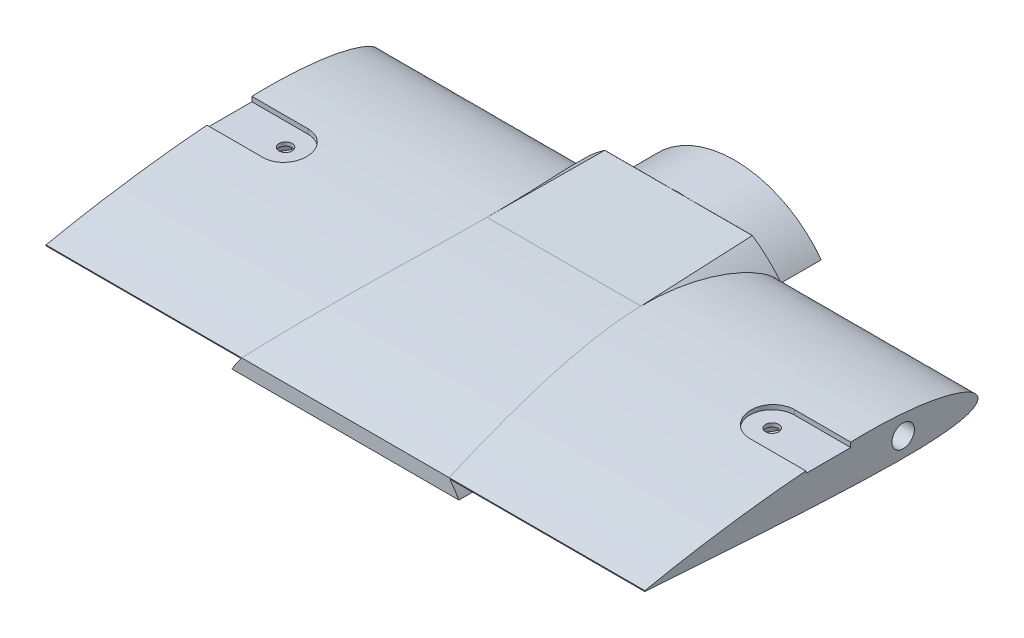
SolidWorks part; units mm, degrees
ref_plane "Front Plane" through (0, 0, 0) normal (0, 0, 1) x (1, 0, 0)
ref_plane "Top Plane" through (0, 0, 0) normal (0, 1, 0) x (1, 0, 0)
ref_plane "Right Plane" through (0, 0, 0) normal (1, 0, 0) x (0, 0, -1)
sketch "Sketch4" plane through (0, 0, 0) normal (0, 0, 1) x (1, 0, 0)
  line L0 (-30.3109, 17.5) -> (30.3109, 17.5)
  arc A1 (30.3109, 17.5) -> (-30.3109, 17.5) centre (0, 0) ccw
  dimension "D1" = 35
  dimension "D2" = 17.5
extrude "Exterior" add sketch "Sketch4" along normal blind 89 contours L0 A1
sketch "Sketch5" plane through (0, 0, 0) normal (0, 0, -1) x (-1, 0, 0)
  line L0 (30.3109, 17.5) -> (-30.3109, 17.5) construction
  line L1 (23.1247, 17.5) -> (-23.1247, 17.5)
  arc A0 (23.1247, 17.5) -> (-23.1247, 17.5) centre (0, 0) ccw
  dimension "D1" = 58
extrude "Boss-Extrude1" add sketch "Sketch5" along normal blind 15
curve "Curve3"
  spline degree 3 poles (0, 1.3, 1000) (0, 4.7133, 983.3426) (0, 11.531, 950.0715) (0, 24.0186, 883.4722) (0, 37.8548, 800.1781) (0, 52.175, 700.1592) (0, 64.1175, 600.1567) (0, 72.8619, 500.1109) (0, 78.7837, 400.0878) (0, 79.786, 316.6355) (0, 77.0249, 249.9395) (0, 72.979, 199.8766) (0, 66.5721, 149.7505) (0, 58.6825, 108.0331) (0, 49.7566, 74.7751) (0, 41.6416, 49.5609) (0, 32.1864, 28.1982) (0, 20.723, 9.771) (0, 0.8988, -6.2982) (0, -16.5264, 10.3934) (0, -24.4739, 28.476) (0, -30.5108, 49.7447) (0, -34.8393, 74.8759) (0, -38.5332, 108.2669) (0, -41.3764, 149.947) (0, -42.5163, 199.9941) (0, -42.3574, 250.0055) (0, -40.8857, 316.6783) (0, -38.2375, 400.0272) (0, -33.6287, 500.0334) (0, -27.6385, 600.0106) (0, -21.4122, 700.0048) (0, -15.1098, 800.0161) (0, -9.3053, 883.3314) (0, -4.8282, 950.0042) (0, -2.4761, 983.334) (0, -1.3, 1000) knots 0 0 0 0 0.025012 0.049959 0.099673 0.149206 0.198581 0.247805 0.296917 0.345953 0.370492 0.395091 0.419815 0.444799 0.45749 0.470406 0.483879 0.491264 0.503459 0.513609 0.520451 0.533235 0.545691 0.558032 0.582609 0.607135 0.631652 0.656174 0.705234 0.75432 0.803437 0.852566 0.901701 0.950849 0.975423 1 1 1 1
sketch "Sketch7" plane through (0, 0, 0) normal (1, 0, 0) x (0, 0, -1)
  line L0 (-89, 21.3887) -> (-89, 21.1573)
  line L1 (-89, 21.273) -> (0, 21.3903) construction
  line L2 (0, 21.3903) -> (-0.0573, 64.8516) construction
  line L7 (-89, 17.5) -> (0, 17.5) construction
  line L9 (0, 17.5) -> (0, 29) construction
  spline S1 degree 3 poles (-89, 21.3887) (-87.5176, 21.6924) (-84.5567, 22.2992) (-78.6297, 23.4105) (-71.2171, 24.6418) (-62.316, 25.9162) (-53.4164, 26.979) (-44.5129, 27.7573) (-35.6114, 28.2842) (-28.1847, 28.3735) (-22.2492, 28.1277) (-17.7939, 27.7677) (-13.3329, 27.1975) (-9.6203, 26.4954) (-6.6606, 25.701) (-4.4167, 24.9788) (-2.5155, 24.1374) (-0.8756, 23.1172) (0.5545, 21.353) (-0.931, 19.8022) (-2.5402, 19.095) (-4.433, 18.5577) (-6.6696, 18.1725) (-9.6412, 17.8438) (-13.3504, 17.5907) (-17.8043, 17.4893) (-22.255, 17.5034) (-28.1885, 17.6344) (-35.606, 17.8701) (-44.506, 18.2802) (-53.4034, 18.8133) (-62.3022, 19.3674) (-71.2026, 19.9283) (-78.6172, 20.4449) (-84.5507, 20.8433) (-87.5168, 21.0526) (-89, 21.1573) knots 0 0 0 0 0.025012 0.049959 0.099673 0.149206 0.198581 0.247805 0.296917 0.345953 0.370492 0.395091 0.419815 0.444799 0.45749 0.470406 0.483879 0.491264 0.503459 0.513609 0.520451 0.533235 0.545691 0.558032 0.582609 0.607135 0.631652 0.656174 0.705234 0.75432 0.803437 0.852566 0.901701 0.950849 0.975423 1 1 1 1
  dimension "D1" = 89
ref_plane "Plane1" through (80, 0, 0) normal (1, 0, 0) x (0, 0, -1)
ref_plane "Plane2" through (-80, 0, 0) normal (1, 0, 0) x (0, 0, -1)
sketch "Sketch8" plane through (80, 0, 0) normal (1, 0, 0) x (0, 0, -1)
  line L0 (-89, 21.3887) -> (-89, 21.1573)
  spline S0 degree 3 poles (-469.3669, 946.2185) (-209.3584, -26.81) (-147.9272, 10.417) (-78.6297, 23.4105) (-71.2171, 24.6418) (-62.316, 25.9162) (-53.4164, 26.979) (-44.5129, 27.7573) (-35.6114, 28.2842) (-28.1847, 28.3735) (-22.2492, 28.1277) (-17.7939, 27.7677) (-13.3329, 27.1975) (-9.6203, 26.4954) (-6.6606, 25.701) (-4.4167, 24.9788) (-2.5155, 24.1374) (-0.8756, 23.1172) (0.5545, 21.353) (-0.931, 19.8022) (-2.5402, 19.095) (-4.433, 18.5577) (-6.6696, 18.1725) (-9.6412, 17.8438) (-13.3504, 17.5907) (-17.8043, 17.4893) (-22.255, 17.5034) (-28.1885, 17.6344) (-35.606, 17.8701) (-44.506, 18.2802) (-53.4034, 18.8133) (-62.3022, 19.3674) (-71.2026, 19.9283) (-78.6172, 20.4449) (-191.4759, 28.0234) (-300.415, 49.2551) (-474.7288, -901.4445) knots -1.065698 -1.065698 -1.065698 -1.065698 0.025012 0.049959 0.099673 0.149206 0.198581 0.247805 0.296917 0.345953 0.370492 0.395091 0.419815 0.444799 0.45749 0.470406 0.483879 0.491264 0.503459 0.513609 0.520451 0.533235 0.545691 0.558032 0.582609 0.607135 0.631652 0.656174 0.705234 0.75432 0.803437 0.852566 0.901701 0.950849 0.975423 2.771414 2.771414 2.771414 2.771414 only from (-89, 21.3887) to (-89, 21.1573) construction
  spline S1 degree 3 poles (-89, 21.3887) (-87.5176, 21.6924) (-84.5567, 22.2992) (-78.6297, 23.4105) (-71.2171, 24.6418) (-62.316, 25.9162) (-53.4164, 26.979) (-44.5129, 27.7573) (-35.6114, 28.2842) (-28.1847, 28.3735) (-22.2492, 28.1277) (-17.7939, 27.7677) (-13.3329, 27.1975) (-9.6203, 26.4954) (-6.6606, 25.701) (-4.4167, 24.9788) (-2.5155, 24.1374) (-0.8756, 23.1172) (0.5545, 21.353) (-0.931, 19.8022) (-2.5402, 19.095) (-4.433, 18.5577) (-6.6696, 18.1725) (-9.6412, 17.8438) (-13.3504, 17.5907) (-17.8043, 17.4893) (-22.255, 17.5034) (-28.1885, 17.6344) (-35.606, 17.8701) (-44.506, 18.2802) (-53.4034, 18.8133) (-62.3022, 19.3674) (-71.2026, 19.9283) (-78.6172, 20.4449) (-84.5507, 20.8433) (-87.5168, 21.0526) (-89, 21.1573) knots 0 0 0 0 0.025012 0.049959 0.099673 0.149206 0.198581 0.247805 0.296917 0.345953 0.370492 0.395091 0.419815 0.444799 0.45749 0.470406 0.483879 0.491264 0.503459 0.513609 0.520451 0.533235 0.545691 0.558032 0.582609 0.607135 0.631652 0.656174 0.705234 0.75432 0.803437 0.852566 0.901701 0.950849 0.975423 1 1 1 1
sketch "Sketch9" plane through (-80, 0, 0) normal (1, 0, 0) x (0, 0, -1)
  line L0 (-89, 21.3887) -> (-89, 21.1573)
  spline S0 degree 3 poles (-469.3669, 946.2185) (-209.3584, -26.81) (-147.9272, 10.417) (-78.6297, 23.4105) (-71.2171, 24.6418) (-62.316, 25.9162) (-53.4164, 26.979) (-44.5129, 27.7573) (-35.6114, 28.2842) (-28.1847, 28.3735) (-22.2492, 28.1277) (-17.7939, 27.7677) (-13.3329, 27.1975) (-9.6203, 26.4954) (-6.6606, 25.701) (-4.4167, 24.9788) (-2.5155, 24.1374) (-0.8756, 23.1172) (0.5545, 21.353) (-0.931, 19.8022) (-2.5402, 19.095) (-4.433, 18.5577) (-6.6696, 18.1725) (-9.6412, 17.8438) (-13.3504, 17.5907) (-17.8043, 17.4893) (-22.255, 17.5034) (-28.1885, 17.6344) (-35.606, 17.8701) (-44.506, 18.2802) (-53.4034, 18.8133) (-62.3022, 19.3674) (-71.2026, 19.9283) (-78.6172, 20.4449) (-191.4759, 28.0234) (-300.415, 49.2551) (-474.7288, -901.4445) knots -1.065698 -1.065698 -1.065698 -1.065698 0.025012 0.049959 0.099673 0.149206 0.198581 0.247805 0.296917 0.345953 0.370492 0.395091 0.419815 0.444799 0.45749 0.470406 0.483879 0.491264 0.503459 0.513609 0.520451 0.533235 0.545691 0.558032 0.582609 0.607135 0.631652 0.656174 0.705234 0.75432 0.803437 0.852566 0.901701 0.950849 0.975423 2.771414 2.771414 2.771414 2.771414 only from (-89, 21.3887) to (-89, 21.1573) construction
  spline S1 degree 3 poles (-89, 21.3887) (-87.5176, 21.6924) (-84.5567, 22.2992) (-78.6297, 23.4105) (-71.2171, 24.6418) (-62.316, 25.9162) (-53.4164, 26.979) (-44.5129, 27.7573) (-35.6114, 28.2842) (-28.1847, 28.3735) (-22.2492, 28.1277) (-17.7939, 27.7677) (-13.3329, 27.1975) (-9.6203, 26.4954) (-6.6606, 25.701) (-4.4167, 24.9788) (-2.5155, 24.1374) (-0.8756, 23.1172) (0.5545, 21.353) (-0.931, 19.8022) (-2.5402, 19.095) (-4.433, 18.5577) (-6.6696, 18.1725) (-9.6412, 17.8438) (-13.3504, 17.5907) (-17.8043, 17.4893) (-22.255, 17.5034) (-28.1885, 17.6344) (-35.606, 17.8701) (-44.506, 18.2802) (-53.4034, 18.8133) (-62.3022, 19.3674) (-71.2026, 19.9283) (-78.6172, 20.4449) (-84.5507, 20.8433) (-87.5168, 21.0526) (-89, 21.1573) knots 0 0 0 0 0.025012 0.049959 0.099673 0.149206 0.198581 0.247805 0.296917 0.345953 0.370492 0.395091 0.419815 0.444799 0.45749 0.470406 0.483879 0.491264 0.503459 0.513609 0.520451 0.533235 0.545691 0.558032 0.582609 0.607135 0.631652 0.656174 0.705234 0.75432 0.803437 0.852566 0.901701 0.950849 0.975423 1 1 1 1
loft "Loft9" add profiles "Sketch8", "Sketch9" connector at (80, 21.3887, 89) connector at (-80, 21.3887, 89)
sketch "Sketch12" plane through (80, 0, 0) normal (1, 0, 0) x (0, 0, -1)
  line L0 (-89, 21.3887) -> (-89, 21.1573) construction
  line L1 (-89, 21.3887) -> (-89, 21.1573)
  line L2 (-89, 21.3887) -> (-97.2409, 26.9065)
  line L3 (-97.2409, 26.9065) -> (-90.2923, 42.7722)
  line L4 (-90.2923, 42.7722) -> (-30.1138, 44.0233)
  line L5 (-30.1138, 44.0233) -> (6.4186, 38.5184)
  line L6 (6.4186, 38.5184) -> (-0.0099, 28.9175)
  line L7 (0, 21.3903) -> (-0.0573, 64.8516) construction
  line L8 (-0.0099, 28.9175) -> (-30.6202, 28.3197)
  spline S0 degree 3 poles (-713.3875, 1915.884) (-239.966, -47.1163) (-164.6221, 7.2867) (-78.6297, 23.4105) (-71.2171, 24.6418) (-62.316, 25.9162) (-53.4164, 26.979) (-44.5129, 27.7573) (-35.6114, 28.2842) (-28.1847, 28.3735) (-22.2492, 28.1277) (-17.7939, 27.7677) (-13.3329, 27.1975) (-9.6203, 26.4954) (-6.6606, 25.701) (-4.4167, 24.9788) (-2.5155, 24.1374) (-0.8756, 23.1172) (0.5545, 21.353) (-0.931, 19.8022) (-2.5402, 19.095) (-4.433, 18.5577) (-6.6696, 18.1725) (-9.6412, 17.8438) (-13.3504, 17.5907) (-17.8043, 17.4893) (-22.255, 17.5034) (-28.1885, 17.6344) (-35.606, 17.8701) (-44.506, 18.2802) (-53.4034, 18.8133) (-62.3022, 19.3674) (-71.2026, 19.9283) (-78.6172, 20.4449) (-220.4152, 29.9667) (-357.7257, 61.3982) (-629.9057, -1889.2617) knots -1.346455 -1.346455 -1.346455 -1.346455 0.025012 0.049959 0.099673 0.149206 0.198581 0.247805 0.296917 0.345953 0.370492 0.395091 0.419815 0.444799 0.45749 0.470406 0.483879 0.491264 0.503459 0.513609 0.520451 0.533235 0.545691 0.558032 0.582609 0.607135 0.631652 0.656174 0.705234 0.75432 0.803437 0.852566 0.901701 0.950849 0.975423 3.250848 3.250848 3.250848 3.250848 only from (-89, 21.3887) to (-89, 21.1573) construction
  spline S1 degree 3 poles (-89, 21.3887) (-87.5176, 21.6924) (-84.5567, 22.2992) (-78.6297, 23.4105) (-71.2171, 24.6418) (-62.316, 25.9162) (-53.4164, 26.979) (-44.5129, 27.7573) (-36.9147, 28.2071) (-32.2817, 28.3107) (-30.6202, 28.3197) knots 0 0 0 0 0.025012 0.049959 0.099673 0.149206 0.198581 0.247805 0.296917 0.324377 0.324377 0.324377 0.324377
  spline S2 degree 3 poles (-89, 21.3887) (-87.5176, 21.6924) (-84.5567, 22.2992) (-78.6297, 23.4105) (-71.2171, 24.6418) (-62.316, 25.9162) (-53.4164, 26.979) (-44.5129, 27.7573) (-36.9147, 28.2071) (-32.2817, 28.3107) (-30.6202, 28.3197) knots 0 0 0 0 0.025012 0.049959 0.099673 0.149206 0.198581 0.247805 0.296917 0.324377 0.324377 0.324377 0.324377
extrude "Cut-Extrude1" cut sketch "Sketch12" against normal through all
sketch "Sketch13" plane through (-80, 0, 0) normal (-1, 0, 0) x (0, 0, 1)
  line L0 (20, 17.5005) -> (20, 27.9379) construction
  circle A0 centre (20, 22.7192) radius 3
  spline S0 degree 3 poles (89, 21.3887) (87.5176, 21.6924) (84.5567, 22.2992) (78.6297, 23.4105) (71.2171, 24.6418) (62.316, 25.9162) (53.4164, 26.979) (44.5129, 27.7573) (35.6114, 28.2842) (28.1847, 28.3735) (22.2492, 28.1277) (17.7939, 27.7677) (13.3329, 27.1975) (9.6203, 26.4954) (6.6606, 25.701) (4.4167, 24.9788) (2.5155, 24.1374) (0.8756, 23.1172) (-0.5545, 21.353) (0.931, 19.8022) (2.5402, 19.095) (4.433, 18.5577) (6.6696, 18.1725) (9.6412, 17.8438) (13.3504, 17.5907) (17.8043, 17.4893) (22.255, 17.5034) (28.1885, 17.6344) (35.606, 17.8701) (44.506, 18.2802) (53.4034, 18.8133) (62.3022, 19.3674) (71.2026, 19.9283) (78.6172, 20.4449) (84.5507, 20.8433) (87.5168, 21.0526) (89, 21.1573) knots 0 0 0 0 0.025012 0.049959 0.099673 0.149206 0.198581 0.247805 0.296917 0.345953 0.370492 0.395091 0.419815 0.444799 0.45749 0.470406 0.483879 0.491264 0.503459 0.513609 0.520451 0.533235 0.545691 0.558032 0.582609 0.607135 0.631652 0.656174 0.705234 0.75432 0.803437 0.852566 0.901701 0.950849 0.975423 1 1 1 1 construction
  point P8 (20, 22.7192)
  dimension "D1" = 6
  dimension "D2" = 20
extrude "Cut-Extrude2" cut sketch "Sketch13" against normal up to surface (160 mm away) up to face at (80, 23.6219, 69.5401)
ref_plane "Plane3" through (0, 30, 0) normal (0, 1, 0) x (1, 0, 0)
sketch "Sketch14" plane through (0, 30, 0) normal (0, 1, 0) x (1, 0, 0)
  line L0 (-95, -34) -> (-65, -34)
  line L1 (-95, -46) -> (-65, -46)
  line L2 (-80, 0) -> (-80, -89) construction
  line L3 (-80, 0) -> (-80, -89) construction
  arc A0 (-65, -46) -> (-65, -34) centre (-65, -40) ccw
  arc A1 (-95, -34) -> (-95, -46) centre (-95, -40) ccw
  point P8 (-80, -34)
  dimension "D2" = 6
  dimension "D1" = 30
  dimension "D3" = 40
extrude "Cut-Extrude3" cut sketch "Sketch14" against normal blind 3 contours L1 A0 L0 L3 | L0 A1 L1 L3 region at (-89.9017, 30, 40) region at (-70.0983, 30, 40)
sketch "Sketch15" plane through (0, 27, 0) normal (0, 1, 0) x (1, 0, 0)
  circle A0 centre (-65, -40) radius 1.75
  dimension "D1" = 3.5
extrude "Cut-Extrude4" cut sketch "Sketch15" against normal blind 4
ref_plane "Plane4" through (0, 23.5, 0) normal (0, 1, 0) x (1, 0, 0)
sketch "Sketch16" plane through (0, 23.5, 0) normal (0, 1, 0) x (1, 0, 0)
  line L1 (-67.1651, -43.75) -> (-62.8349, -43.75)
  line L2 (-62.8349, -43.75) -> (-60.6699, -40)
  line L3 (-60.6699, -40) -> (-62.8349, -36.25)
  line L4 (-62.8349, -36.25) -> (-67.1651, -36.25)
  line L5 (-67.1651, -36.25) -> (-69.3301, -40)
  line L6 (-69.3301, -40) -> (-67.1651, -43.75)
  circle A0 centre (-65, -40) radius 3.75 construction
  dimension "D1" = 7.5
extrude "Cut-Extrude5" cut sketch "Sketch16" along normal blind 2.5
mirror "Mirror1" about plane through (0, 0, 0) normal (1, 0, 0) of "Cut-Extrude5", "Cut-Extrude4", "Cut-Extrude3"
equation "\"fuse_diam\"= 0.07"
equation "\"fuse_rad\"= 0.035"
equation "\"battery_length\"= 0.076"
equation "\"battery_width\"= 0.034"
equation "\"battery_height\"= 0.051"
equation "\"bat_bay_length\"= 0.096"
equation "\"shell\"= 0.002"
equation "\"D1@Exterior\"=\"chord_length\""
equation "\"wing_shelf\"= 0.0175"
equation "\"chord_length\"= 0.089"
equation "\"tail_length\"= 0.26532000000000006"
equation "\"tail_diam\"= 0.035"
equation "\"connector\"= 0.06633000000000001"
equation "\"D2@Sketch4\"=\"wing_shelf\""
equation "\"D1@Sketch4\"=\"fuse_rad\""
equation "\"D1@Sketch5\"=\"fuse_diam\"-0.012"
equation "\"D1@Sketch7\"=\"chord_length\""
